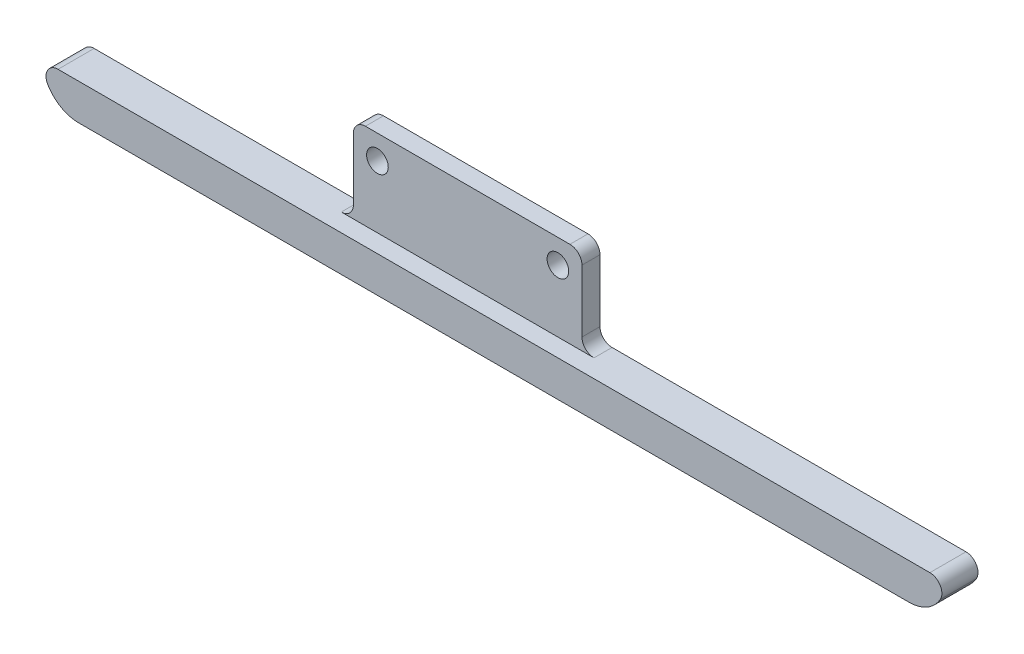
SolidWorks part; units mm, degrees
ref_plane "Front Plane" through (0, 0, 0) normal (0, 0, 1) x (1, 0, 0)
ref_plane "Top Plane" through (0, 0, 0) normal (0, 1, 0) x (1, 0, 0)
ref_plane "Right Plane" through (0, 0, 0) normal (1, 0, 0) x (0, 0, -1)
sketch "Sketch1" plane through (0, 0, 0) normal (0, 0, 1) x (1, 0, 0)
  line L0 (0, 0) -> (0, 6)
  line L1 (0, 6) -> (150, 6)
  line L2 (150, 6) -> (150, 0)
  line L3 (150, 0) -> (0, 0)
  line L4 (48.63, 6) -> (48.63, 20.35)
  line L5 (48.63, 20.35) -> (86.63, 20.35)
  line L6 (86.63, 20.35) -> (86.63, 6)
  line L7 (48.63, 16.35) -> (86.63, 16.35) construction
  line L8 (75, 0) -> (75, 6) construction
  dimension "D1" = 6
  dimension "D2" = 150
  dimension "D3" = 10.35
  dimension "D4" = 4
  dimension "D5" = 38
  dimension "D6" = 11.63
extrude "Boss-Extrude1" add sketch "Sketch1" along normal blind 6 contours L3 L2 L1 L0 region at (75, 3, 0)
extrude "Boss-Extrude2" add sketch "Sketch1<3>" along normal blind 3 contours L6 L5 L4 L1 region at (67.63, 13.175, 0)
sketch "Sketch1<3>" plane through (0, 0, 0) normal (0, 0, 1) x (1, 0, 0) same geometry as "Sketch1"
hole_wizard "M3 Clearance Hole1" positions "Sketch4" profile "Sketch3" hole size "M3" standard "ANSI Metric" end condition through all
sketch "Sketch4" plane through (0, 0, 3) normal (0, 0, 1) x (1, 0, 0)
  line L0 (48.63, 16.35) -> (86.63, 16.35) construction
  line L1 (48.63, 6) -> (48.63, 20.35) construction
  line L2 (86.63, 20.35) -> (86.63, 6) construction
  point P0 (52.63, 16.35)
  point P4 (82.63, 16.35)
  dimension "D1" = 4
  dimension "D2" = 4
sketch "Sketch3" plane through (52.63, 16.35, 3) normal (1, 0, 0) x (0, -1, 0)
  line L0 (0, 0) -> (0, 3)
  line L1 (0, 3) -> (1.8, 3)
  line L2 (1.8, 3) -> (1.8, 0)
  line L5 (1.8, 0) -> (0, 0)
  line L11 (0, -6.35) -> (0, 107.95) construction
  dimension "Thru Hole Dia." = 3.6
  dimension "Thru Hole Depth" = 3
fillet "Fillet1" radius 6 2 edges at (150, 0, 3) (0, 0, 3)
fillet "Fillet2" radius 2 6 edges at (150, 6, 3) (86.63, 6, 1.5) (48.63, 6, 1.5) (86.63, 20.35, 1.5) (48.63, 20.35, 1.5) (0, 6, 3)
mirror "Mirror1" [suppressed] about plane through (0, 0, 0) normal (0, 0, 1) of bodies 103
delete or keep bodies "Body-Delete/Keep 1" [suppressed] type delete bodies bodies 103
